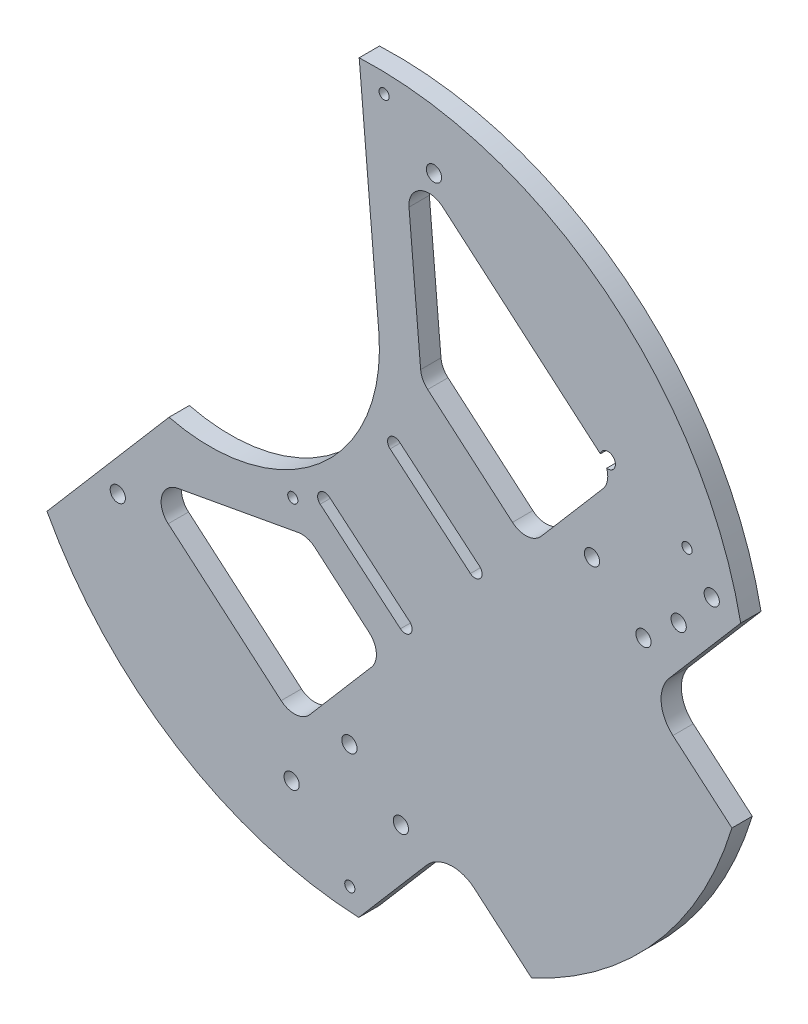
SolidWorks part; units mm, degrees
material "PMMA"
ref_plane "Front Plane" through (0, 0, 0) normal (0, 0, 1) x (1, 0, 0)
ref_plane "Top Plane" through (0, 0, 0) normal (0, 1, 0) x (1, 0, 0)
ref_plane "Right Plane" through (0, 0, 0) normal (1, 0, 0) x (0, 0, -1)
sketch "Sketch1" plane through (0, 0, 0) normal (0, 0, 1) x (1, 0, 0)
  line L0 (-65.0357, 1.7119) -> (-29.0137, 43.7635)
  line L1 (27.0989, 163.6983) -> (32.8912, 96.5787)
  arc A5 (-65.0357, 1.7119) -> (27.0989, 163.6983) centre (31.8495, 53.8009) ccw
  arc A6 (-29.0137, 43.7635) -> (32.8912, 96.5787) centre (-16.9236, 92.2798) ccw
  circle A7 centre (-44.1307, 16.5884) radius 2.25
  circle A8 centre (7.1608, -31.0475) radius 2.25
  circle A9 centre (100.4703, 97.5518) radius 2.25
  circle A10 centre (49.1788, 145.1877) radius 2.25
  dimension "D1" = 220
  dimension "D2" = 100
  dimension "D6" = 4.5
  dimension "D3" = 60.8633
  dimension "D4" = 55.3707
  dimension "D5" = 67.1195
extrude "Boss-Extrude1" add sketch "Sketch1" along normal blind 6
sketch "Sketch2" plane through (0, 0, 6) normal (0, 0, 1) x (1, 0, 0)
  line L0 (61.2734, 49.8977) -> (37.5872, 69.8968) construction
  line L1 (59.9186, 48.2932) -> (36.2324, 68.2923)
  line L2 (62.6282, 51.5023) -> (38.942, 71.5014)
  line L3 (40.6292, 25.4474) -> (16.943, 45.4465) construction
  line L4 (39.2744, 23.8429) -> (15.5882, 43.842)
  line L5 (41.984, 27.052) -> (18.2978, 47.0511)
  line L6 (61.2734, 49.8977) -> (46.5625, 32.4747) construction
  line L7 (46.5625, 32.4747) -> (37.9334, 22.2547) construction
  line L8 (15.0411, 41.8646) -> (37.8247, 22.3478) construction
  line L9 (50.2278, 38.2835) -> (29.8022, 55.5295) construction
  line L11 (16.943, 45.4465) -> (37.5872, 69.8968) construction
  arc A0 (59.9186, 48.2932) -> (62.6282, 51.5023) centre (61.2734, 49.8977) ccw
  arc A1 (38.942, 71.5014) -> (36.2324, 68.2923) centre (37.5872, 69.8968) ccw
  arc A2 (39.2744, 23.8429) -> (41.984, 27.052) centre (40.6292, 25.4474) ccw
  arc A3 (18.2978, 47.0511) -> (15.5882, 43.842) centre (16.943, 45.4465) ccw
  circle A5 centre (58.207, 52.2904) radius 2.25 construction
  point P4 (49.4303, 59.8973)
  point P9 (28.7861, 35.447)
  dimension "D1" = 4.2
  dimension "D2" = 4.2
  dimension "D3" = 25
  dimension "D4" = 16
  dimension "D5" = 32
  dimension "D6" = 31
  dimension "D7" = 31
  dimension "D8" = 16
extrude "Cut-Extrude1" cut sketch "Sketch2" against normal blind 10
hole_wizard "Ø4.5 (4.5) Diameter Hole" positions "Sketch3" profile "Sketch4" hole size "Ø4.5" standard "IS"
sketch "Sketch3" plane through (207.2158, -96.42, 6) normal (0, 0, 1) x (-0.6506, -0.7595, 0)
  point P0 (80.5001, -194.4616)
  point P3 (77.6909, -264.4052)
  point P6 (-80.6779, -277.2022)
  point P9 (-77.8687, -207.2586)
sketch "Sketch4" plane through (7.1608, -31.0475, 6) normal (1, 0, 0) x (0, -1, 0)
  line L0 (0, 0) -> (0, 11.3519)
  line L1 (0, 11.3519) -> (2.25, 10)
  line L2 (2.25, 10) -> (2.25, 0)
  line L3 (2.25, 0) -> (0, 0)
  line L4 (0, 11.3519) -> (-2.25, 10) construction
  line L5 (0, -6.35) -> (0, 107.95) construction
  dimension "Hole Dia." = 4.5
  dimension "Hole Depth" = 10
  dimension "Drill Angle" = 118
hole_wizard "Ø3.0mm Dowel Hole1" positions "Sketch5" profile "Sketch6" hole size "Ø3.0" standard "IS" end condition through all
sketch "Sketch5" plane through (207.2158, -96.42, 6) normal (0, 0, 1) x (-0.6506, -0.7595, 0)
  point P0 (-80.9158, -296.795)
  point P3 (-84.9452, -182.5189)
  point P6 (25.2163, -241.3641)
  point P9 (83.3286, -169.4245)
sketch "Sketch6" plane through (34.4537, 158.1146, 6) normal (1, 0, 0) x (0, -1, 0)
  line L0 (0, 0) -> (0, 6)
  line L1 (0, 6) -> (1.5, 6)
  line L2 (1.5, 6) -> (1.5, 0)
  line L3 (1.5, 0) -> (0, 0)
  line L4 (0, -6.35) -> (0, 107.95) construction
  dimension "Thru Hole Dia." = 3
  dimension "Thru Hole Depth" = 6
sketch "Sketch7" plane through (0, 0, 6) normal (0, 0, 1) x (1, 0, 0)
  line L0 (139.6892, 75.4943) -> (26.9717, -56.0909) construction
  line L1 (41.8033, 132.8778) -> (45.2389, 93.0663)
  line L2 (37.8247, 22.3478) -> (46.282, 32.2207) construction
  line L3 (139.6892, 75.4943) -> (118.5944, 50.8684)
  line L4 (119.6834, 36.7683) -> (137.1053, 21.8444)
  line L5 (84.7002, 70.5146) -> (146.9827, 12.671) construction
  line L6 (137.1053, 21.8444) -> (157.1792, 45.2784)
  line L7 (157.1792, 45.2784) -> (139.6892, 75.4943)
  line L8 (26.9717, -56.0909) -> (47.0048, -32.7045)
  line L9 (61.105, -31.6155) -> (77.9709, -46.0631)
  line L10 (23.454, 4.5684) -> (85.7366, -53.2753) construction
  line L11 (77.9709, -46.0631) -> (19.4206, -114.4141)
  line L12 (19.4206, -114.4141) -> (26.9717, -56.0909)
  line L13 (39.4103, -26.1989) -> (110.9998, 57.374) construction
  line L14 (110.9998, 57.374) -> (95.8107, 70.3852) construction
  line L15 (95.8107, 70.3852) -> (24.2212, -13.1877) construction
  line L16 (24.2212, -13.1877) -> (39.4103, -26.1989) construction
  line L17 (121.3842, 66.4224) -> (131.1426, 77.8142) construction
  line L22 (47.3134, 89.0254) -> (72.3436, 67.5842)
  line L23 (80.8037, 68.2376) -> (99.0194, 89.5024)
  line L24 (98.366, 97.9624) -> (51.6844, 137.9504)
  line L26 (27.0989, 163.6983) -> (32.8912, 96.5787) construction
  line L28 (78.8002, 120.3667) -> (69.4931, 129.4392) construction
  line L29 (30.0871, 18.2544) -> (14.0299, 32.0092)
  line L30 (9.0496, 33.355) -> (-26.4328, 26.8812)
  line L31 (-29.2593, 16.422) -> (4.0648, -12.1238)
  line L32 (12.5249, -11.4704) -> (30.7405, 9.7943)
  line L33 (17.6296, -27.1227) -> (8.104, -18.2761) construction
  line L35 (-29.0137, 43.7635) -> (-65.0357, 1.7119) construction
  arc A0 (-65.0357, 1.7119) -> (27.0989, 163.6983) centre (31.8495, 53.8009) ccw construction
  arc A1 (72.3436, 67.5842) -> (80.8037, 68.2376) centre (76.247, 72.1409) ccw
  circle A2 centre (34.4537, 158.1146) radius 1.6 construction
  arc A3 (118.5944, 50.8684) -> (119.6834, 36.7683) centre (126.1889, 44.3629) ccw
  arc A4 (47.0048, -32.7045) -> (61.105, -31.6155) centre (54.5994, -39.2101) cw
  circle A5 centre (39.4103, -26.1989) radius 2.25
  circle A6 centre (110.9998, 57.374) radius 2.25
  circle A7 centre (24.2212, -13.1877) radius 2.25
  circle A8 centre (95.8107, 70.3852) radius 2.25
  circle A9 centre (121.3842, 66.4224) radius 2.25
  circle A10 centre (131.1426, 77.8142) radius 2.25
  arc A11 (45.2389, 93.0663) -> (47.3134, 89.0254) centre (51.2167, 93.5822) ccw
  arc A12 (41.8033, 132.8778) -> (51.6844, 137.9504) centre (47.7811, 133.3937) cw
  arc A13 (99.0194, 89.5024) -> (98.366, 97.9624) centre (94.4626, 93.4057) ccw
  arc A14 (14.0299, 32.0092) -> (9.0496, 33.355) centre (10.1266, 27.4525) ccw
  arc A15 (30.0871, 18.2544) -> (30.7405, 9.7943) centre (26.1838, 13.6977) cw
  arc A16 (4.0648, -12.1238) -> (12.5249, -11.4704) centre (7.9681, -7.5671) ccw
  arc A17 (-26.4328, 26.8812) -> (-29.2593, 16.422) centre (-25.3559, 20.9787) ccw
  point P22 (112.0888, 43.2739)
  point P25 (53.5104, -25.1099)
  point P55 (76.9004, 63.6809)
  point P62 (102.9227, 94.0591)
  point P65 (11.8602, 33.8678)
  point P68 (34.6439, 14.3511)
  point P71 (8.6215, -16.0272)
  point P74 (-38.8291, 24.6195)
  dimension "D8" = 10
  dimension "D9" = 4.5
  dimension "D26" = 6
  dimension "D1" = 214.3362
  dimension "D2" = 90
  dimension "D3" = 90
  dimension "D4" = 90
  dimension "D5" = 30.8563
  dimension "D6" = 90
  dimension "D7" = 90
  dimension "D10" = 20
  dimension "D11" = 10
  dimension "D12" = 10
  dimension "D13" = 10
  dimension "D14" = 8
  dimension "D15" = 15
  dimension "D16" = 15.5539
  dimension "D17" = 12
  dimension "D18" = 2
  dimension "D19" = 40
  dimension "D20" = 40
  dimension "D21" = 40
  dimension "D22" = 2
  dimension "D23" = 40
  dimension "D24" = 5
  dimension "D25" = 30
extrude "Cut-Extrude2" cut sketch "Sketch7" against normal blind 10
